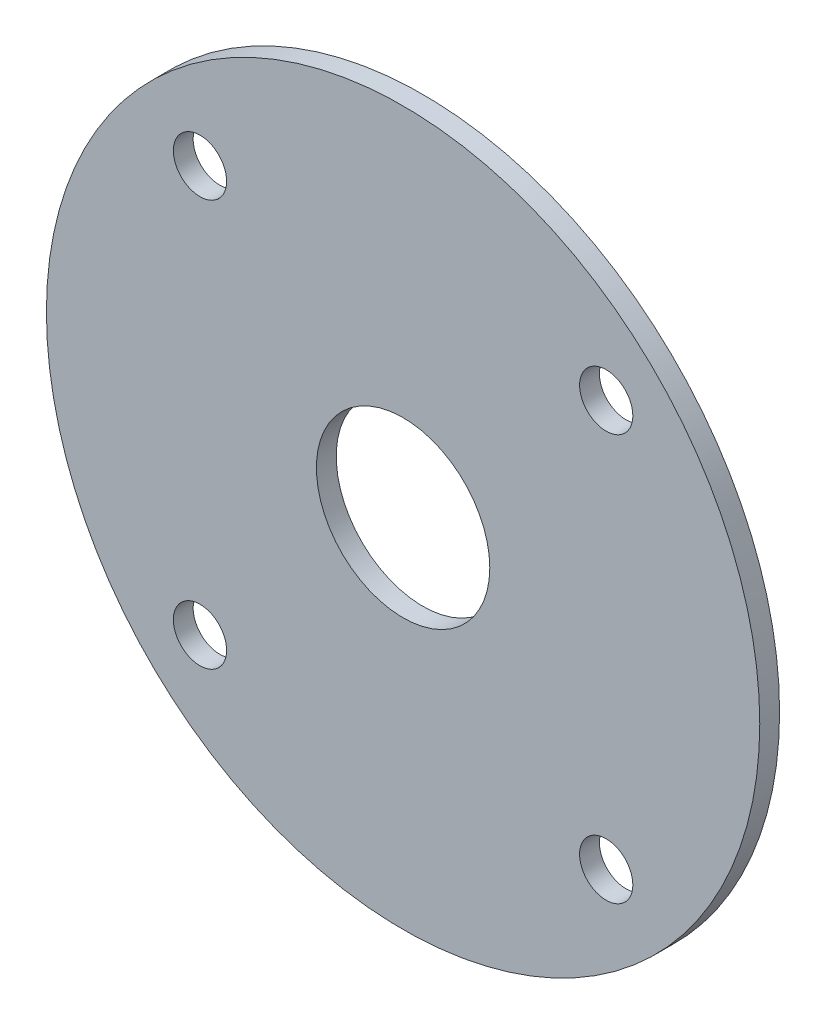
SolidWorks part; units mm, degrees
ref_plane "Front Plane" through (0, 0, 0) normal (0, 0, 1) x (1, 0, 0)
ref_plane "Top Plane" through (0, 0, 0) normal (0, 1, 0) x (1, 0, 0)
ref_plane "Right Plane" through (0, 0, 0) normal (1, 0, 0) x (0, 0, -1)
sketch "Sketch2" plane through (0, 0, 0) normal (0, 0, 1) x (1, 0, 0)
  circle A0 centre (0, 0) radius 114.3
  circle A1 centre (0, 0) radius 27.7813
  dimension "D1" = 228.6
  dimension "D2" = 55.5625
extrude "Extrude1" add sketch "Sketch2" along normal blind 6.35
sketch "Sketch3" plane through (0, 0, 6.35) normal (0, 0, 1) x (1, 0, 0)
  circle A0 centre (-65.0875, -65.0875) radius 8.5328
  circle A1 centre (-65.0875, 65.0875) radius 8.5328
  circle A2 centre (65.0875, 65.0875) radius 8.5328
  circle A3 centre (65.0875, -65.0875) radius 8.5328
  circle A4 centre (65.0875, -65.0875) radius 8.5328 construction
  circle A5 centre (-65.0875, -65.0875) radius 8.5328 construction
  circle A6 centre (-65.0875, 65.0875) radius 8.5328 construction
  circle A7 centre (65.0875, 65.0875) radius 8.5328 construction
extrude "Cut-Extrude1" cut sketch "Sketch3" against normal up to next
